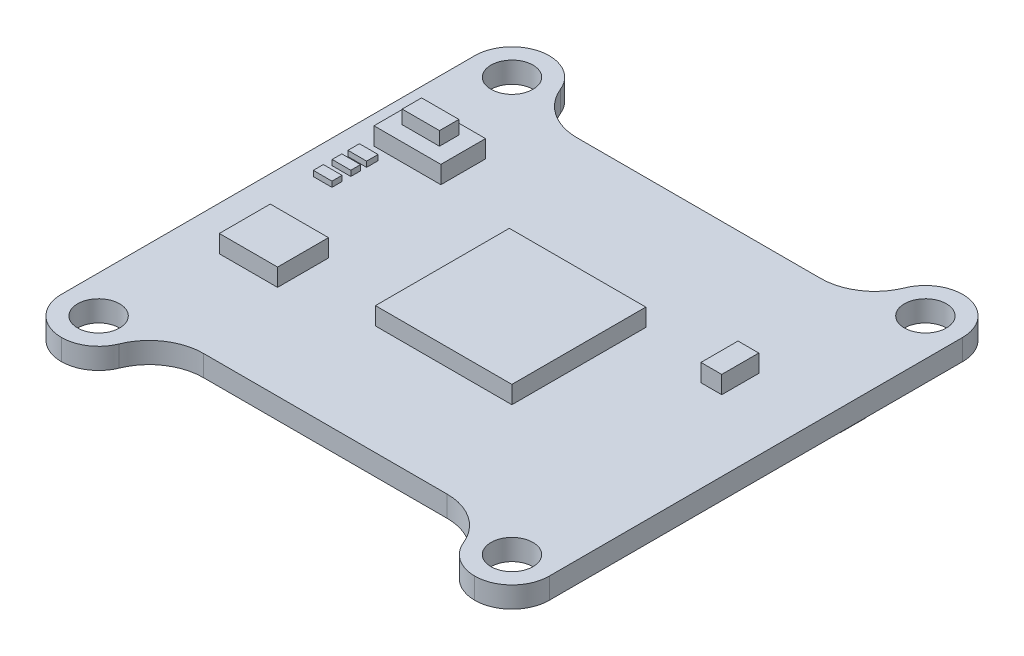
SolidWorks part; units mm, degrees
ref_plane "Front Plane" through (0, 0, 0) normal (0, 0, 1) x (1, 0, 0)
ref_plane "Top Plane" through (0, 0, 0) normal (0, 1, 0) x (1, 0, 0)
ref_plane "Right Plane" through (0, 0, 0) normal (1, 0, 0) x (0, 0, -1)
sketch "Sketch1" plane through (0, 0, 0) normal (0, 1, 0) x (1, 0, 0)
  line L0 (0, 18) -> (0, -15.25) construction
  line L1 (-18, 18) -> (18, 18)
  line L2 (-18, 18) -> (-18, -18)
  line L3 (-18, -18) -> (18, -18)
  line L4 (18, 18) -> (18, -18)
  line L5 (-18, 18) -> (18, -18) construction
  line L6 (-18, -18) -> (18, 18) construction
  line L7 (-15.25, 15.25) -> (15.25, 15.25) construction
  line L8 (-15.25, 15.25) -> (-15.25, -15.25) construction
  line L9 (-15.25, -15.25) -> (15.25, -15.25) construction
  line L10 (15.25, 15.25) -> (15.25, -15.25) construction
  line L11 (-15.25, 15.25) -> (15.25, -15.25) construction
  line L12 (-15.25, -15.25) -> (15.25, 15.25) construction
  line L13 (-18, 0) -> (18, 0) construction
  line L14 (0, 13.78) -> (0, 18) construction
  line L15 (-12.5, 18) -> (12.5, 18)
  line L16 (-12.5, 18) -> (-12.5, 13.78)
  line L17 (-12.5, 13.78) -> (12.5, 13.78)
  line L18 (12.5, 18) -> (12.5, 13.78)
  line L19 (-12.5, -18) -> (12.5, -18)
  line L20 (-12.5, -18) -> (-12.5, -13.78)
  line L21 (-12.5, -13.78) -> (12.5, -13.78)
  line L22 (12.5, -18) -> (12.5, -13.78)
  line L23 (0, -13.78) -> (0, -18) construction
  circle A0 centre (-15.25, 15.25) radius 1.55
  circle A1 centre (15.25, 15.25) radius 1.55
  circle A2 centre (15.25, -15.25) radius 1.55
  circle A3 centre (-15.25, -15.25) radius 1.55
  point P0 (0, 0)
  point P6 (0, 0)
  dimension "D3" = 3.1
  dimension "D1" = 30.5
  dimension "D2" = 36
  dimension "D4" = 27.56
  dimension "D5" = 25
extrude "Boss-Extrude1" add sketch "Sketch1" along normal blind 1.55 contours L22 L3 L4 L1 L18 L17 L16 L2 L20 L21 A1 A0 A2 A3 region at (0, 0, 0)
fillet "Fillet1" radius 2.75 8 edges at (-12.5, 0.775, -18) (-18, 0.775, -18) (-18, 0.775, 18) (-12.5, 0.775, 18) (12.5, 0.775, 18) (18, 0.775, 18) (18, 0.775, -18) (12.5, 0.775, -18)
fillet "Fillet2" radius 4 4 edges at (12.5, 0.775, -13.78) (-12.5, 0.775, -13.78) (12.5, 0.775, 13.78) (-12.5, 0.775, 13.78)
sketch "Sketch2" plane through (0, 1.55, 0) normal (0, 1, 0) x (1, 0, 0)
  line L1 (-14.7636, -3.0707) -> (-10.468, -3.0707)
  line L2 (-14.7636, -3.0707) -> (-14.7636, -6.8293)
  line L3 (-14.7636, -6.8293) -> (-10.468, -6.8293)
  line L4 (-10.468, -3.0707) -> (-10.468, -6.8293)
  line L5 (5.6741, 4.1978) -> (-4.3937, 4.1978)
  line L6 (5.6741, 4.1978) -> (5.6741, -5.6823)
  line L7 (5.6741, -5.6823) -> (-4.3937, -5.6823)
  line L8 (-4.3937, 4.1978) -> (-4.3937, -5.6823)
  line L9 (11.2445, 5.4301) -> (12.7777, 5.4301)
  line L10 (11.2445, 5.4301) -> (11.2445, 2.6971)
  line L11 (11.2445, 2.6971) -> (12.7777, 2.6971)
  line L12 (12.7777, 5.4301) -> (12.7777, 2.6971)
  line L13 (-15.9382, 9.0526) -> (-11.0049, 9.0526)
  line L14 (-15.9382, 9.0526) -> (-15.9382, 5.7564)
  line L15 (-15.9382, 5.7564) -> (-11.0049, 5.7564)
  line L16 (-11.0049, 9.0526) -> (-11.0049, 5.7564)
extrude "Boss-Extrude2" add sketch "Sketch2" along normal blind 1.3
sketch "Sketch3" plane through (0, 2.85, 0) normal (0, 1, 0) x (1, 0, 0)
  line L1 (-14.9649, 8.2941) -> (-12.2131, 8.2941)
  line L2 (-14.9649, 8.2941) -> (-14.9649, 6.8629)
  line L3 (-14.9649, 6.8629) -> (-12.2131, 6.8629)
  line L4 (-12.2131, 8.2941) -> (-12.2131, 6.8629)
extrude "Boss-Extrude3" add sketch "Sketch3" along normal blind 1
sketch "Sketch5" plane through (0, 0, 0) normal (0, -1, 0) x (1, 0, 0)
  line L0 (-18, -15.25) -> (-18, 15.25) construction
  line L1 (-2.8633, 8.1258) -> (-18, 8.1258)
  line L2 (-2.8633, 8.1258) -> (-2.8633, -6.5377)
  line L3 (-2.8633, -6.5377) -> (-18, -6.5377)
  line L4 (-18, 8.1258) -> (-18, -6.5377)
  line L6 (10.6737, -7.0481) -> (14.4599, -7.0481)
  line L7 (10.6737, -7.0481) -> (10.6737, -10.2981)
  line L8 (10.6737, -10.2981) -> (14.4599, -10.2981)
  line L9 (14.4599, -7.0481) -> (14.4599, -10.2981)
  line L10 (14.8141, -4.2672) -> (12.9599, -4.2672)
  line L11 (14.8141, -4.2672) -> (14.8141, -1.2929)
  line L12 (14.8141, -1.2929) -> (12.9599, -1.2929)
  line L13 (12.9599, -4.2672) -> (12.9599, -1.2929)
  line L14 (11.7978, -3.6591) -> (10.6737, -3.6591)
  line L15 (11.7978, -3.6591) -> (11.7978, -1.8268)
  line L16 (11.7978, -1.8268) -> (10.6737, -1.8268)
  line L17 (10.6737, -3.6591) -> (10.6737, -1.8268)
  line L18 (0.4152, -4.2672) -> (-2.464, -4.2672)
  line L19 (0.4152, -4.2672) -> (0.4152, -3.0397)
  line L20 (0.4152, -3.0397) -> (-2.464, -3.0397)
  line L21 (-2.464, -4.2672) -> (-2.464, -3.0397)
  line L22 (0.4152, 1.5138) -> (-1.0244, 1.5138)
  line L23 (0.4152, 1.5138) -> (0.4152, 4.1579)
  line L24 (0.4152, 4.1579) -> (-1.0244, 4.1579)
  line L25 (-1.0244, 1.5138) -> (-1.0244, 4.1579)
  line L26 (16.6623, -9.463) -> (15.5994, -9.463)
  line L27 (16.6623, -9.463) -> (16.6623, -7.5612)
  line L28 (16.6623, -7.5612) -> (15.5994, -7.5612)
  line L29 (15.5994, -9.463) -> (15.5994, -7.5612)
extrude "Boss-Extrude5" add sketch "Sketch5" along normal blind 1.36
sketch "Sketch6" plane through (0, 1.55, 0) normal (0, 1, 0) x (1, 0, 0)
  line L1 (-16.23, 4.9722) -> (-14.853, 4.9722)
  line L2 (-16.23, 4.9722) -> (-16.23, 4.1248)
  line L3 (-16.23, 4.1248) -> (-14.853, 4.1248)
  line L4 (-14.853, 4.9722) -> (-14.853, 4.1248)
  line L5 (-16.23, 4.9722) -> (-14.853, 4.1248) construction
  line L6 (-16.23, 4.1248) -> (-14.853, 4.9722) construction
  line L7 (-16.23, 3.6746) -> (-14.853, 3.6746)
  line L8 (-16.23, 3.6746) -> (-16.23, 2.9596)
  line L9 (-16.23, 2.9596) -> (-14.853, 2.9596)
  line L10 (-14.853, 3.6746) -> (-14.853, 2.9596)
  line L11 (-16.23, 3.6746) -> (-14.853, 2.9596) construction
  line L12 (-16.23, 2.9596) -> (-14.853, 3.6746) construction
  line L13 (-16.23, 2.3108) -> (-14.853, 2.3108)
  line L14 (-16.23, 2.3108) -> (-16.23, 1.5693)
  line L15 (-16.23, 1.5693) -> (-14.853, 1.5693)
  line L16 (-14.853, 2.3108) -> (-14.853, 1.5693)
  line L17 (-16.23, 2.3108) -> (-14.853, 1.5693) construction
  line L18 (-16.23, 1.5693) -> (-14.853, 2.3108) construction
  point P4 (-15.5415, 4.5485)
  point P9 (-15.5415, 3.3171)
  point P14 (-15.5415, 1.94)
extrude "LED" add sketch "Sketch6" along normal blind 0.4
